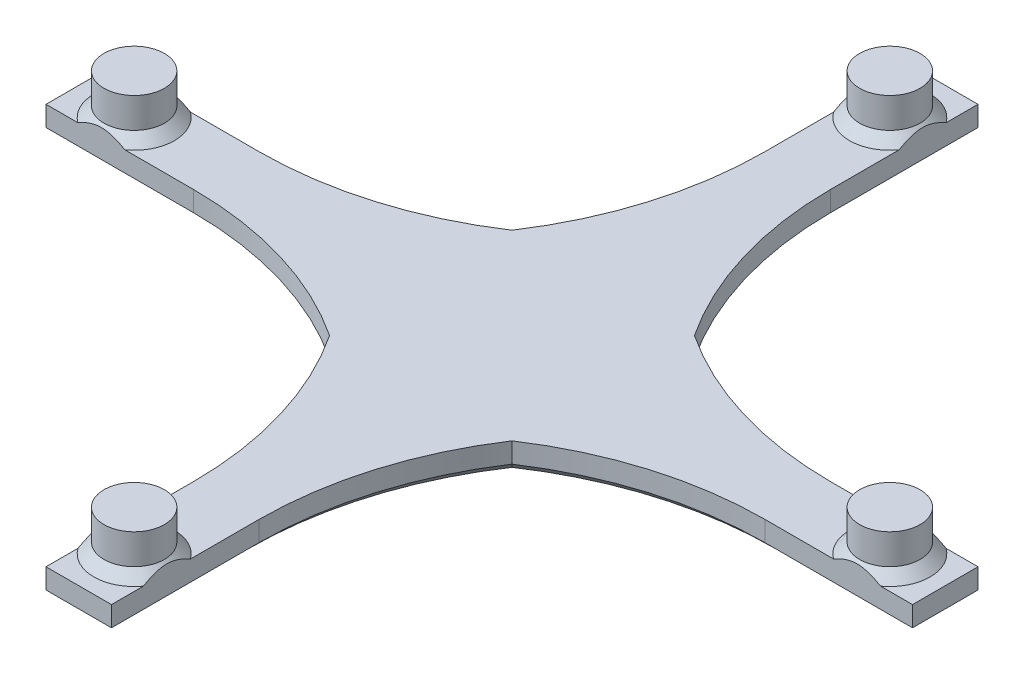
SolidWorks part; units mm, degrees
material "ABS"
ref_plane "Front Plane" through (0, 0, 0) normal (0, 0, 1) x (1, 0, 0)
ref_plane "Top Plane" through (0, 0, 0) normal (0, 1, 0) x (1, 0, 0)
ref_plane "Right Plane" through (0, 0, 0) normal (1, 0, 0) x (0, 0, -1)
sketch "Sketch1" plane through (0, 0, 0) normal (0, 1, 0) x (1, 0, 0)
  circle A0 centre (0, 0) radius 3
  dimension "D1" = 6
extrude "Boss-Extrude1" add sketch "Sketch1" against normal blind 4
sketch "Sketch2" plane through (0, 0, 0) normal (0, 1, 0) x (1, 0, 0)
  line L0 (-3.25, 43) -> (-3.25, 13.8566)
  line L1 (-43, -43) -> (43, -43) construction
  line L2 (-43, -43) -> (-43, 43) construction
  line L3 (-43, 43) -> (43, 43) construction
  line L4 (43, -43) -> (43, 43) construction
  line L5 (-43, -43) -> (43, 43) construction
  line L6 (-43, 43) -> (43, -43) construction
  line L7 (-3.25, 13.8566) -> (-13.8566, 3.25)
  line L8 (-13.8566, 3.25) -> (-43, 3.25)
  line L9 (-43, 3.25) -> (-43, -3.25)
  line L10 (-43, -3.25) -> (-13.8566, -3.25)
  line L11 (-13.8566, -3.25) -> (-3.25, -13.8566)
  line L12 (-3.25, -13.8566) -> (-3.25, -43)
  line L13 (-3.25, -43) -> (3.25, -43)
  line L14 (3.25, -43) -> (3.25, -13.8566)
  line L15 (3.25, -13.8566) -> (13.8566, -3.25)
  line L16 (13.8566, -3.25) -> (43, -3.25)
  line L17 (43, -3.25) -> (43, 3.25)
  line L18 (43, 3.25) -> (13.8566, 3.25)
  line L19 (13.8566, 3.25) -> (3.25, 13.8566)
  line L20 (3.25, 13.8566) -> (3.25, 43)
  line L21 (3.25, 43) -> (-3.25, 43)
  point P0 (0, 0)
  point P19 (0, 43)
  point P23 (0, -43)
  point P24 (-43, 0)
  point P25 (43, 0)
  dimension "D1" = 6.5
  dimension "D2" = 15
  dimension "D3" = 86
extrude "Boss-Extrude2" add sketch "Sketch2" along normal blind 3
sketch "Sketch3" plane through (0, 3, 0) normal (0, 1, 0) x (1, 0, 0)
  line L0 (0, 37.5) -> (0, -37.5) construction
  line L1 (37.5, 0) -> (-37.5, 0) construction
  circle A0 centre (-37.5, 0) radius 3
  circle A1 centre (0, 37.5) radius 3
  circle A2 centre (37.5, 0) radius 3
  circle A3 centre (0, -37.5) radius 3
  point P8 (0, 0)
  point P9 (0, 0)
  dimension "D1" = 6
  dimension "D2" = 75
extrude "Boss-Extrude3" add sketch "Sketch3" along normal blind 4
fillet "Fillet2" radius 35 8 edges at (-13.8566, 1.5, -3.25) (-3.25, 1.5, -13.8566) (3.25, 1.5, -13.8566) (13.8566, 1.5, -3.25) (13.8566, 1.5, 3.25) (3.25, 1.5, 13.8566) (-13.8566, 1.5, 3.25) (-3.25, 1.5, 13.8566)
chamfer "Chamfer1" distance 1 angle 45 4 edges at (-37.5, 3, 3) (37.5, 3, 3) (0, 3, 40.5) (0, 3, -34.5)
chamfer "Chamfer2" distance 1 angle 45 20 edges at (-35.677, 0, -3.25) (-18.2768, 0, -4.7321) (-4.7321, 0, -18.2768) (-3.25, 0, -35.677) (3.25, 0, -35.677) (4.7321, 0, -18.2768) (18.2768, 0, -4.7321) (35.677, 0, -3.25) (35.677, 0, 3.25) (18.2768, 0, 4.7321) (4.7321, 0, 18.2768) (3.25, 0, 35.677) (-3.25, 0, 35.677) (-4.7321, 0, 18.2768) (-18.2768, 0, 4.7321) (-35.677, 0, 3.25) (0, 0, -43) (43, 0, 0) (0, 0, 43) (-43, 0, 0)
